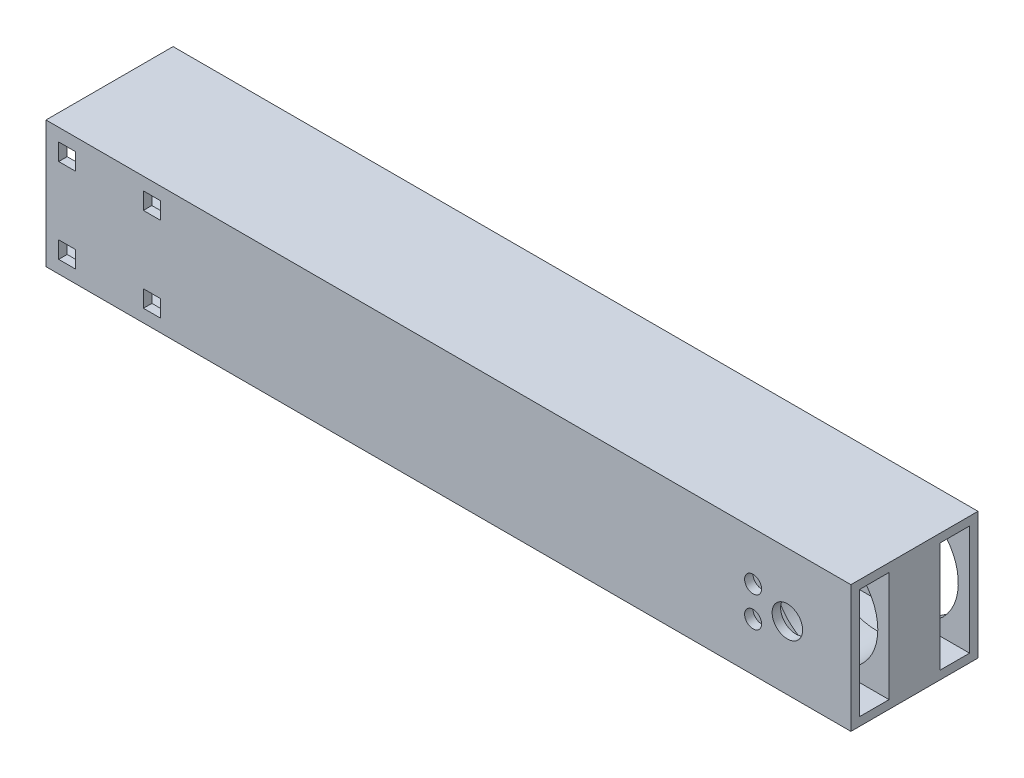
SolidWorks part; units mm, degrees
ref_plane "Front Plane" through (0, 0, 0) normal (0, 0, 1) x (1, 0, 0)
ref_plane "Top Plane" through (0, 0, 0) normal (0, 1, 0) x (1, 0, 0)
ref_plane "Right Plane" through (0, 0, 0) normal (1, 0, 0) x (0, 0, -1)
sketch "Sketch1" plane through (0, 0, 0) normal (1, 0, 0) x (0, 0, -1)
  line L1 (-15, -15) -> (15, -15)
  line L2 (-15, -15) -> (-15, 15)
  line L3 (-15, 15) -> (15, 15)
  line L4 (15, -15) -> (15, 15)
  line L5 (-15, -15) -> (15, 15) construction
  line L6 (-15, 15) -> (15, -15) construction
  line L11 (-5.1844, 5.1844) -> (5.1844, -5.1844) construction
  line L12 (-5.1844, -5.1844) -> (5.1844, 5.1844) construction
  line L13 (-13, 13) -> (-6, 13)
  line L14 (-13, 13) -> (-13, -13)
  line L15 (-13, -13) -> (-6, -13)
  line L16 (-6, 13) -> (-6, -13)
  line L17 (13, 13) -> (6, 13)
  line L18 (13, 13) -> (13, -13)
  line L19 (13, -13) -> (6, -13)
  line L20 (6, 13) -> (6, -13)
  point P0 (0, 0)
  point P7 (0, 0)
  dimension "D1" = 30
  dimension "D2" = 30
  dimension "D3" = 2
  dimension "D4" = 7
  dimension "D5" = 2
  dimension "D6" = 7
  dimension "D7" = 2
  dimension "D8" = 2
extrude "Boss-Extrude3" add sketch "Sketch1" along normal blind 110 and the other way blind 80
sketch "Sketch6" plane through (0, 0, -15) normal (0, 0, -1) x (-1, 0, 0)
  line L0 (-110, -15) -> (-110, 15) construction
  circle A0 centre (-95, 0) radius 12.35
  dimension "D2" = 24.7
  dimension "D1" = 15
extrude "Cut-Extrude5" cut sketch "Sketch6" against normal blind 23
sketch "Sketch8" plane through (0, 0, 15) normal (0, 0, 1) x (1, 0, 0)
  line L0 (110, 15) -> (110, -15) construction
  circle A0 centre (95, 0) radius 3.6
  circle A1 centre (86.9069, 3.5812) radius 2
  circle A2 centre (86.9069, -3.5812) radius 2
  dimension "D2" = 7.2
  dimension "D5" = 4
  dimension "D6" = 4
  dimension "D1" = 15
  dimension "D3" = 8.85
  dimension "D4" = 8.85
extrude "Cut-Extrude6" cut sketch "Sketch8" against normal blind 17
sketch "Sketch9" plane through (-80, 0, 0) normal (-1, 0, 0) x (0, 0, 1)
  line L0 (-6, 13) -> (6, 13)
  line L1 (-6, -13) -> (6, -13)
  line L2 (-6, 13) -> (-6, -13)
  line L3 (6, 13) -> (6, -13)
extrude "Cut-Extrude7" cut sketch "Sketch9" against normal blind 106
sketch "Sketch12" plane through (0, 0, 15) normal (0, 0, 1) x (1, 0, 0)
  line L0 (-80, 15) -> (110, 15) construction
  line L1 (-80, 15) -> (-80, -15) construction
  line L2 (-80, 15) -> (-50, 15) construction
  line L3 (-50, 15) -> (-50, -15) construction
  line L5 (-80, -15) -> (110, -15) construction
  line L6 (-77, 8) -> (-73, 8)
  line L7 (-77, 8) -> (-77, 12)
  line L8 (-77, 12) -> (-73, 12)
  line L9 (-73, 8) -> (-73, 12)
  line L10 (-77, 8) -> (-73, 12) construction
  line L11 (-77, 12) -> (-73, 8) construction
  line L12 (-57.0136, 8) -> (-52.9864, 8)
  line L13 (-57.0136, 8) -> (-57.0136, 12)
  line L14 (-57.0136, 12) -> (-52.9864, 12)
  line L15 (-52.9864, 8) -> (-52.9864, 12)
  line L16 (-57.0136, 8) -> (-52.9864, 12) construction
  line L17 (-57.0136, 12) -> (-52.9864, 8) construction
  line L18 (-57, -12) -> (-53, -12)
  line L19 (-57, -12) -> (-57, -8)
  line L20 (-57, -8) -> (-53, -8)
  line L21 (-53, -12) -> (-53, -8)
  line L22 (-57, -12) -> (-53, -8) construction
  line L23 (-57, -8) -> (-53, -12) construction
  line L24 (-77, -12) -> (-73, -12)
  line L25 (-77, -12) -> (-77, -8)
  line L26 (-77, -8) -> (-73, -8)
  line L27 (-73, -12) -> (-73, -8)
  line L28 (-77, -12) -> (-73, -8) construction
  line L29 (-77, -8) -> (-73, -12) construction
  circle A2 centre (-55, 10) radius 2
  circle A3 centre (-75, -10) radius 2
  circle A4 centre (-55, -10) radius 2
  dimension "D3" = 4
  dimension "D7" = 4
  dimension "D9" = 4
  dimension "D11" = 4
  dimension "D2" = 4
  dimension "D4" = 5
  dimension "D5" = 30
  dimension "D6" = 5
  dimension "D8" = 5
  dimension "D10" = 5
  dimension "D12" = 20
  dimension "D13" = 5
  dimension "D14" = 4
extrude "Cut-Extrude8" cut sketch "Sketch12" against normal blind 40 contours L8 L9 L6 L7 | L14 L15 L12 L13 | L20 L21 L18 L19 | L26 L27 L24 L25
